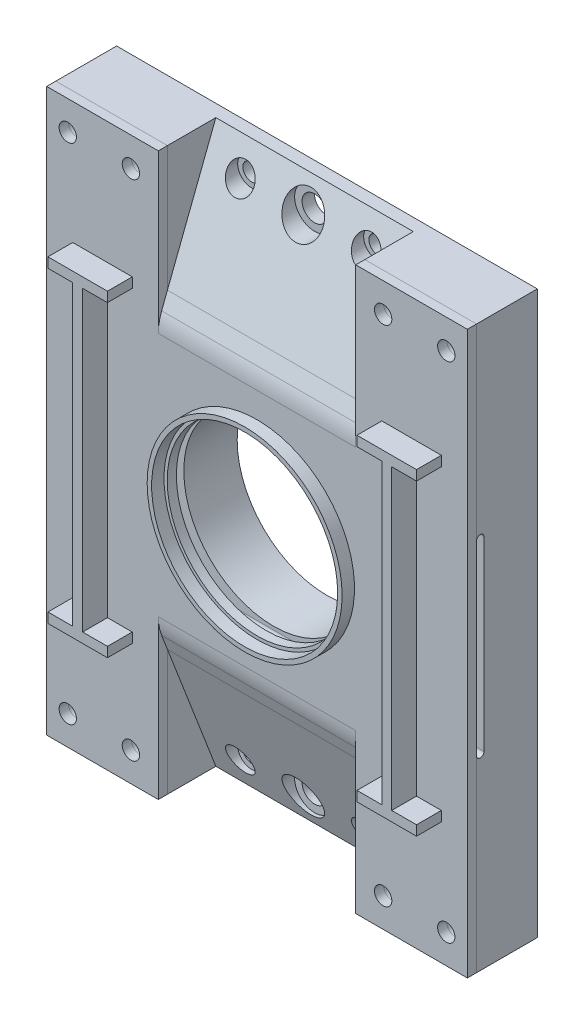
SolidWorks part; units mm, degrees
note: The reader was unsure of these and kept them because the rebuilt part matched: shared geometry of "Croquis1<2>", "Croquis1<3>".
ref_plane "Alzado" through (0, 0, 0) normal (0, 0, 1) x (1, 0, 0)
ref_plane "Planta" through (0, 0, 0) normal (0, 1, 0) x (1, 0, 0)
ref_plane "Vista lateral" through (0, 0, 0) normal (1, 0, 0) x (0, 0, -1)
sketch "Croquis1" plane through (0, 0, 0) normal (0, 0, 1) x (1, 0, 0)
  line L1 (-39.8, -113.25) -> (39.8, -113.25)
  line L2 (-39.8, -113.25) -> (-39.8, 113.25)
  line L3 (-39.8, 113.25) -> (39.8, 113.25)
  line L4 (39.8, -113.25) -> (39.8, 113.25)
  line L5 (-39.8, -113.25) -> (39.8, 113.25) construction
  line L6 (-39.8, 113.25) -> (39.8, -113.25) construction
  circle A0 centre (-50.85, -101.5) radius 3.5
  circle A1 centre (0, 101.5) radius 5.05
  circle A2 centre (-25.4, 101.5) radius 3.5
  circle A3 centre (-76.3, -101.5) radius 3.5
  circle A4 centre (25.4, 101.5) radius 3.5
  circle A5 centre (25.4, -101.5) radius 3.5
  circle A6 centre (0, -101.5) radius 5.05
  circle A7 centre (-25.4, -101.5) radius 3.5
  circle A8 centre (0, 0) radius 36.2
  circle A9 centre (50.85, -101.5) radius 3.5
  circle A10 centre (76.3, -101.5) radius 3.5
  circle A11 centre (-76.3, 101.5) radius 3.5
  circle A12 centre (-50.85, 101.5) radius 3.5
  circle A13 centre (50.85, 101.5) radius 3.5
  circle A14 centre (76.3, 101.5) radius 3.5
  point P0 (0, 0)
extrude "Saliente-Extruir1" add sketch "Croquis1" along normal blind 5
sketch "Croquis2" plane through (0, 0, 5) normal (0, 0, 1) x (1, 0, 0)
  line L1 (39.8, -113.25) -> (-39.8, -113.25)
  line L2 (39.8, -113.25) -> (39.8, 113.25)
  line L3 (39.8, 113.25) -> (-39.8, 113.25)
  line L4 (-39.8, -113.25) -> (-39.8, 113.25)
  line L5 (39.8, -113.25) -> (-39.8, 113.25) construction
  line L6 (39.8, 113.25) -> (-39.8, -113.25) construction
  circle A0 centre (0, 0) radius 36.2
  circle A1 centre (-25.4, 101.5) radius 5.6
  circle A2 centre (0, 101.5) radius 8.05
  circle A3 centre (25.4, 101.5) radius 5.6
  circle A4 centre (-25.4, -101.5) radius 5.6
  circle A6 centre (25.4, -101.5) radius 5.6
  circle A7 centre (0, -101.5) radius 8.05
  point P0 (0, 0)
  dimension "D1" = 72.4
extrude "Saliente-Extruir2" add sketch "Croquis2" along normal blind 23.2
sketch "Croquis3" plane through (39.8, 0, 0) normal (1, 0, 0) x (0, 0, -1)
  line L0 (-5, -113.25) -> (-28.2, -113.25)
  line L1 (-28.2, -113.25) -> (0, -113.25) construction
  line L2 (-28.2, -113.25) -> (-28.2, -53.1214)
  line L3 (-28.2, -113.25) -> (-28.2, 113.25) construction
  line L4 (-28.2, -53.1214) -> (-5, -113.25)
  line L5 (-24.52, -113.25) -> (-34.3156, -113.25) construction
extrude "Cortar-Extruir1" cut sketch "Croquis3" against normal blind 80
sketch "Croquis4" plane through (39.8, 0, 0) normal (1, 0, 0) x (0, 0, -1)
  line L0 (-28.2, 113.25) -> (-5, 113.25)
  line L1 (-28.2, 113.25) -> (-28.2, 53.25)
  line L2 (-28.2, -53.1214) -> (-28.2, 113.25) construction
  line L3 (-28.2, 113.25) -> (0, 113.25) construction
  line L4 (-28.2, 53.25) -> (-5, 113.25)
extrude "Cortar-Extruir3" cut sketch "Croquis4" against normal blind 80
fillet "Redondeo1" radius 20 1 edges at (0, 53.25, 28.2)
fillet "Redondeo2" radius 20 1 edges at (0, -53.1214, 28.2)
sketch "Croquis6" plane through (0, 0, 28.2) normal (0, 0, 1) x (1, 0, 0)
  line L5 (39.9478, -49.7018) -> (-39.8, 49.518) construction
  line L6 (39.8, 49.8206) -> (-39.8, -49.8206) construction
  point P0 (0, 0)
sketch "Croquis10" plane through (0, -113.25, 0) normal (0, -1, 0) x (1, 0, 0)
  line L0 (0, 23.02) -> (-37.5, 23.02)
  line L1 (-37.5, 23.02) -> (-37.5, 21.52)
  line L2 (0, 0) -> (0, 23.02)
  line L3 (5.05, 0) -> (-5.05, 0) construction
  line L4 (0, 23.02) -> (37.5, 23.02)
  line L6 (37.5, 23.02) -> (-37.5, 23.02) construction
  line L7 (37.5, 21.52) -> (-37.5, 21.52)
  line L8 (37.5, 24.52) -> (-37.5, 24.52)
  line L10 (39.8, 24.52) -> (-39.8, 24.52)
  line L11 (-39.8, 24.52) -> (-39.8, 34.3156)
  line L12 (39.8, 24.52) -> (39.8, 34.3156)
  arc A0 (37.5, 21.52) -> (37.5, 24.52) centre (37.5, 23.02) ccw
  arc A1 (-37.5, 24.52) -> (-37.5, 21.52) centre (-37.5, 23.02) ccw
  point P3 (0, 23.02)
sketch "Croquis11" plane through (39.8, 0, 0) normal (1, 0, 0) x (0, 0, -1)
  line L0 (0, 113.25) -> (0, -113.25) construction
  line L1 (0, -113.25) -> (-28.2, -113.25)
  line L2 (0, -113.25) -> (0, 113.25)
  line L3 (0, 113.25) -> (-28.2, 113.25)
  line L4 (-28.2, -113.25) -> (-28.2, 113.25)
  dimension "D1" = 226.5
extrude "Saliente-Extruir3" add sketch "Croquis11" along normal blind 45
extrude "Cortar-Extruir7" cut sketch "Croquis1<2>" along normal blind 45 contours A10 | A9 | A13 | A14
sketch "Croquis1<2>" plane through (0, 0, 0) normal (0, 0, 1) x (1, 0, 0) same geometry as "Croquis1"
sketch "Croquis13" plane through (-39.8, 0, 0) normal (-1, 0, 0) x (0, 0, 1)
  line L0 (28.2, 49.518) -> (28.2, -49.3969) construction
  line L1 (0, 113.25) -> (28.2, 113.25)
  line L2 (0, 113.25) -> (0, -113.25)
  line L3 (0, -113.25) -> (28.2, -113.25)
  line L4 (28.2, 113.25) -> (28.2, -113.25)
extrude "Saliente-Extruir4" add sketch "Croquis13" along normal blind 45
extrude "Cortar-Extruir8" cut sketch "Croquis1<3>" along normal blind 45 contours A0 | A11 | A3 | A12
sketch "Croquis1<3>" plane through (0, 0, 0) normal (0, 0, 1) x (1, 0, 0) same geometry as "Croquis1"
sketch "Croquis15" plane through (0, 0, 28.2) normal (0, 0, 1) x (1, 0, 0)
  circle A0 centre (-50.85, 101.5) radius 5.6
  circle A1 centre (-76.3, 101.5) radius 5.6
  circle A2 centre (50.85, 101.5) radius 5.6
  circle A3 centre (76.3, 101.5) radius 5.6
  circle A4 centre (-76.3, -101.5) radius 5.6
  circle A5 centre (-50.85, -101.5) radius 5.6
  circle A6 centre (50.85, -101.5) radius 5.6
  circle A7 centre (76.3, -101.5) radius 5.6
sketch "Croquis20" plane through (0, 0, 28.2) normal (0, 0, 1) x (1, 0, 0)
  circle A0 centre (0, 0) radius 37.5
  circle A1 centre (0, 0) radius 39.3
sketch "Croquis21" plane through (0, 0, 28.2) normal (0, 0, 1) x (1, 0, 0)
  line L0 (-64.3, -60) -> (-74.3, -60)
  line L1 (0, 80) -> (-80, 80) construction
  line L2 (-80, 80) -> (-80, -80) construction
  line L3 (-80, -80) -> (80, -80) construction
  line L4 (80, -80) -> (80, 80) construction
  line L5 (0, 80) -> (80, 80) construction
  line L7 (-64.3, 60) -> (-64.3, -60)
  line L8 (-64.3, 60) -> (-74.3, 60)
  line L9 (-60.3, -60) -> (-60.3, 60)
  line L11 (50.3, 64) -> (50.3, 60)
  line L12 (-74.3, -60) -> (-74.3, -64)
  line L13 (-74.3, -64) -> (-64.3, -64)
  line L14 (-64.3, -64) -> (-50.3, -64)
  line L15 (-50.3, -64) -> (-50.3, -60)
  line L16 (-50.3, -60) -> (-60.3, -60)
  line L17 (-74.3, 60) -> (-74.3, 64)
  line L18 (-74.3, 64) -> (-50.3, 64)
  line L19 (-50.3, 64) -> (-50.3, 60)
  line L20 (-50.3, 60) -> (-60.3, 60)
  line L21 (74.3, 64) -> (50.3, 64)
  line L22 (74.3, 60) -> (74.3, 64)
  line L23 (64.3, 60) -> (74.3, 60)
  line L24 (50.3, 60) -> (60.3, 60)
  line L25 (60.3, -60) -> (60.3, 60)
  line L26 (64.3, 60) -> (64.3, -60)
  line L27 (64.3, -60) -> (74.3, -60)
  line L28 (74.3, -60) -> (74.3, -64)
  line L29 (74.3, -64) -> (64.3, -64)
  line L30 (64.3, -64) -> (50.3, -64)
  line L31 (50.3, -64) -> (50.3, -60)
  line L32 (50.3, -60) -> (60.3, -60)
extrude "Saliente-Extruir7" add sketch "Croquis21" along normal blind 10
sketch "Croquis17" plane through (0, -113.25, 0) normal (0, -1, 0) x (1, 0, 0)
  line L0 (0, 24.52) -> (-39.8, 24.52)
  line L1 (37.5, 24.52) -> (-37.5, 24.52) construction
  line L2 (0, 24.52) -> (39.8, 24.52)
  line L3 (39.8, 24.52) -> (39.8, 68.9643)
  line L4 (-39.8, 24.52) -> (-39.8, 67.2912)
sketch "Croquis22" plane through (84.8, 0, 0) normal (1, 0, 0) x (0, 0, -1)
  line L3 (-23.02, -37.5) -> (-23.02, 37.5) construction
  line L5 (-24.52, -37.5) -> (-24.52, 37.5)
  line L6 (-21.52, -37.5) -> (-21.52, 37.5)
  arc A0 (-24.52, -37.5) -> (-21.52, -37.5) centre (-23.02, -37.5) ccw
  arc A1 (-21.52, 37.5) -> (-24.52, 37.5) centre (-23.02, 37.5) ccw
  point P15 (-23.02, 0)
extrude "Cortar-Extruir9" cut sketch "Croquis22" against normal blind 125
sketch "Croquis23" plane through (84.8, 0, 0) normal (1, 0, 0) x (0, 0, -1)
  line L0 (-24.52, 0) -> (-24.52, -120)
  line L1 (-24.52, 37.5) -> (-24.52, -37.5) construction
  line L2 (-24.52, 0) -> (-24.52, 124.1074)
split "Partir3" trim tools "Croquis23" bodies to split 142 resulting bodies 147 148
extrude "Saliente-Extruir8" add sketch "Croquis20" along normal blind 5
split "Partir4" trim tools "Croquis23" bodies to split 147 152 resulting bodies 150 151
